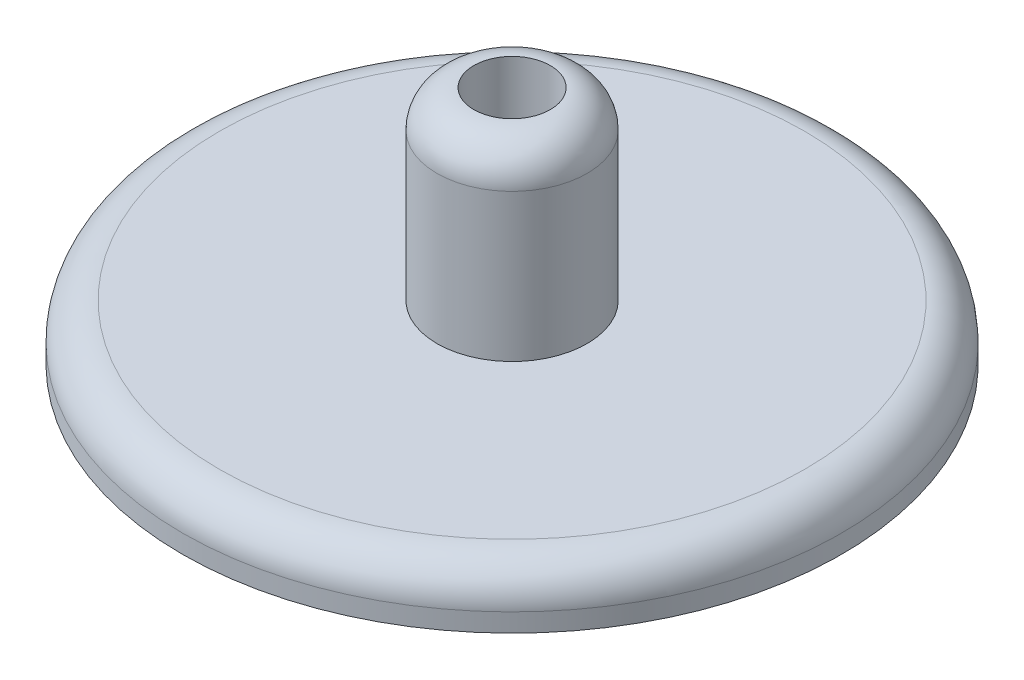
SolidWorks part; units mm, degrees
ref_plane "Front Plane" through (0, 0, 0) normal (0, 0, 1) x (1, 0, 0)
ref_plane "Top Plane" through (0, 0, 0) normal (0, 1, 0) x (1, 0, 0)
ref_plane "Right Plane" through (0, 0, 0) normal (1, 0, 0) x (0, 0, -1)
sketch "Sketch1" plane through (0, 0, 0) normal (0, 1, 0) x (1, 0, 0)
  circle A0 centre (-18.1789, 33.9076) radius 17.89
  circle A1 centre (-18.1789, 33.9076) radius 2.075
  circle A2 centre (-18.1789, 33.9076) radius 4.075
  dimension "D1" = 35.78
  dimension "D2" = 4.15
  dimension "D3" = 2
extrude "Boss-Extrude1" add sketch "Sketch1" along normal blind 3 contours A0 A2 | A2 A1 | A1 region at (-35.5629, 0, -33.9076) region at (-18.1789, 0, -33.9076) region at (-22.1386, 0, -33.9076)
extrude "Boss-Extrude2" add sketch "Sketch1<4>" along normal blind 5 from surface contours A2 A1 | A1 region at (-18.1789, 0, -33.9076) region at (-22.1386, 0, -33.9076) starting at face at (-18.1789, 3, -16.0176)
sketch "Sketch1<4>" plane through (0, 0, 0) normal (0, 1, 0) x (1, 0, 0) same geometry as "Sketch1"
extrude "Boss-Extrude3" add sketch "Sketch1<5>" along normal blind 5 from surface contours A2 A1 region at (-22.1386, 0, -33.9076) starting at face at (-18.1789, 8, -29.8326)
sketch "Sketch1<5>" plane through (0, 0, 0) normal (0, 1, 0) x (1, 0, 0) same geometry as "Sketch1"
fillet "Fillet1" radius 2 2 edges at (-18.1789, 3, -16.0176) (-18.1789, 13, -29.8326)
